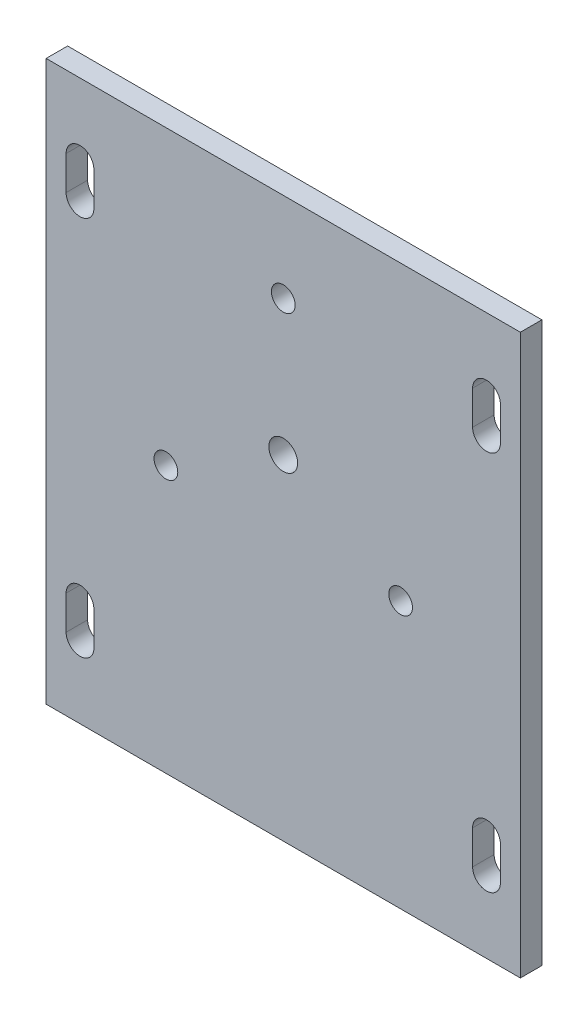
SolidWorks part; units mm, degrees
ref_plane "Front Plane" through (0, 0, 0) normal (0, 0, 1) x (1, 0, 0)
ref_plane "Top Plane" through (0, 0, 0) normal (0, 1, 0) x (1, 0, 0)
ref_plane "Right Plane" through (0, 0, 0) normal (1, 0, 0) x (0, 0, -1)
sketch "Sketch1" plane through (0, 0, 0) normal (0, 0, 1) x (1, 0, 0)
  line L0 (0, 38.1) -> (0, -38.1) construction
  line L1 (-35, -38.1) -> (35, -38.1)
  line L2 (-35, -38.1) -> (-35, 38.1)
  line L3 (-35, 38.1) -> (35, 38.1)
  line L4 (35, -38.1) -> (35, 38.1)
  line L5 (-35, -38.1) -> (35, 38.1) construction
  line L6 (-35, 38.1) -> (35, -38.1) construction
  line L7 (-35, 0) -> (35, 0) construction
  line L8 (-35, 28.1) -> (0, 28.1) construction
  line L9 (-30, 25.6) -> (-30, 30.6) construction
  line L10 (-32.05, 25.6) -> (-32.05, 30.6)
  line L11 (-27.95, 25.6) -> (-27.95, 30.6)
  line L12 (30, 25.6) -> (30, 30.6) construction
  line L13 (32.05, 25.6) -> (32.05, 30.6)
  line L14 (27.95, 25.6) -> (27.95, 30.6)
  line L15 (-30, -25.6) -> (-30, -30.6) construction
  line L16 (-32.05, -25.6) -> (-32.05, -30.6)
  line L17 (-27.95, -25.6) -> (-27.95, -30.6)
  line L18 (30, -25.6) -> (30, -30.6) construction
  line L19 (32.05, -25.6) -> (32.05, -30.6)
  line L20 (27.95, -25.6) -> (27.95, -30.6)
  circle A0 centre (-30, 28.1) radius 2.05 construction
  arc A1 (-32.05, 25.6) -> (-27.95, 25.6) centre (-30, 25.6) ccw
  arc A2 (-27.95, 30.6) -> (-32.05, 30.6) centre (-30, 30.6) ccw
  arc A3 (32.05, 25.6) -> (27.95, 25.6) centre (30, 25.6) cw
  arc A4 (27.95, 30.6) -> (32.05, 30.6) centre (30, 30.6) cw
  arc A5 (-32.05, -25.6) -> (-27.95, -25.6) centre (-30, -25.6) cw
  arc A6 (-27.95, -30.6) -> (-32.05, -30.6) centre (-30, -30.6) cw
  arc A7 (32.05, -25.6) -> (27.95, -25.6) centre (30, -25.6) ccw
  arc A8 (27.95, -30.6) -> (32.05, -30.6) centre (30, -30.6) ccw
  circle A10 centre (0, 8.1) radius 20 construction
  circle A11 centre (0, 28.1) radius 1.75
  circle A12 centre (17.3205, -1.9) radius 1.75
  circle A13 centre (-17.3205, -1.9) radius 1.75
  circle A14 centre (0, 8.1) radius 2.125
  circle A15 centre (0, 8.1) radius 33.35 construction
  point P0 (0, 0)
  point P16 (-30, 28.1)
  point P24 (30, 28.1)
  point P31 (-30, -28.1)
  point P38 (30, -28.1)
  point P52 (0, 8.1)
  dimension "D4" = 4.1
  dimension "D6" = 2.05
  dimension "D7" = 40
  dimension "D9" = 3.5
  dimension "D11" = 4.25
  dimension "D12" = 66.7
  dimension "D1" = 76.2
  dimension "D2" = 70
  dimension "D3" = 10
  dimension "D5" = 5
  dimension "D8" = 46.2
  dimension "D13" = 5
  dimension "D10" = 3
extrude "Boss-Extrude1" add sketch "Sketch1" along normal blind 3.175
sketch "Sketch3" plane through (0, 0, 3.175) normal (0, 0, 1) x (1, 0, 0)
  line L0 (0, 0) -> (62.8834, 0) construction
  line L1 (-35, 38.1) -> (35, 38.1)
  line L2 (-35, 38.1) -> (-35, 41.275)
  line L3 (-35, 41.275) -> (35, 41.275)
  line L4 (35, 38.1) -> (35, 41.275)
  line L5 (-35, -41.275) -> (35, -41.275)
  line L6 (35, -38.1) -> (35, -41.275)
  line L7 (-35, -38.1) -> (35, -38.1)
  line L8 (-35, -38.1) -> (-35, -41.275)
  dimension "D1" = 3.175
extrude "Boss-Extrude2" add sketch "Sketch3" against normal up to surface (3.175 mm away) up to face at (19.0705, -1.9, 0)
